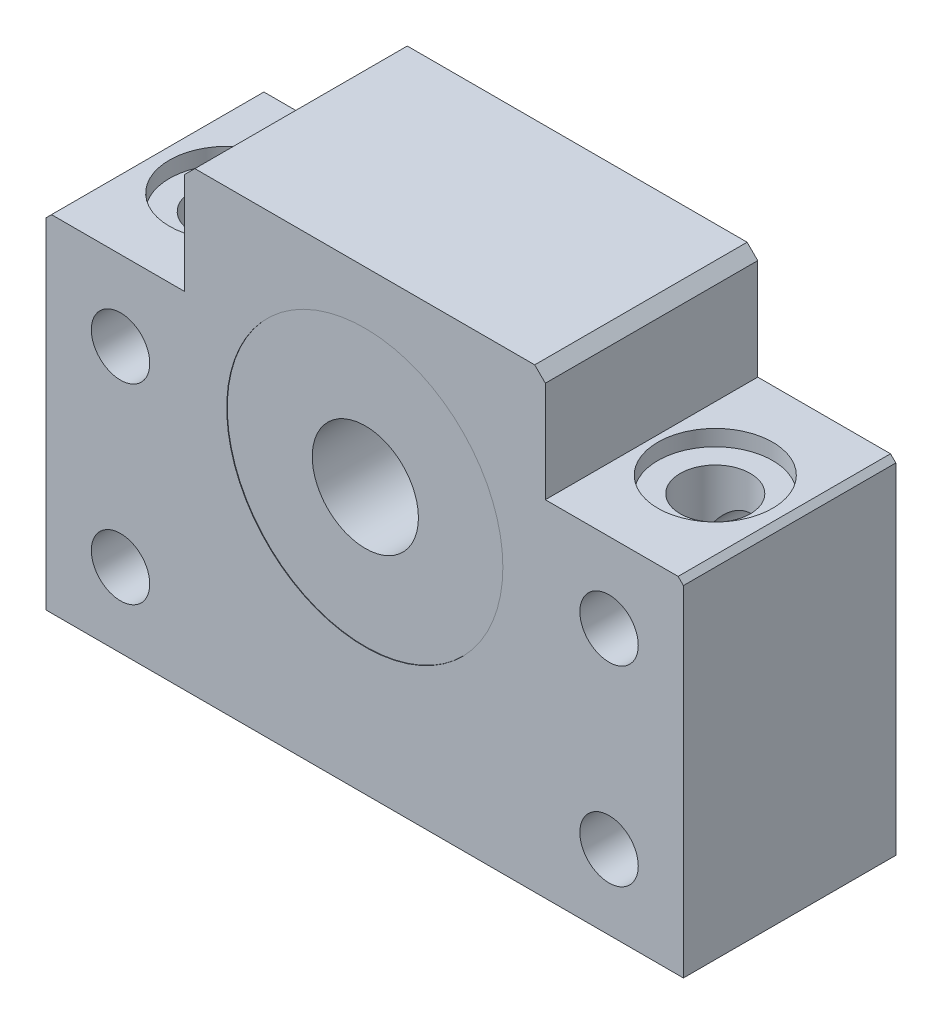
SolidWorks part; units mm, degrees
material "6061-T6 (SS)"
ref_plane "Спереди" through (0, 0, 0) normal (0, 0, 1) x (1, 0, 0)
ref_plane "Сверху" through (0, 0, 0) normal (0, 1, 0) x (1, 0, 0)
ref_plane "Справа" through (0, 0, 0) normal (1, 0, 0) x (0, 0, -1)
sketch "Эскиз1" plane through (0, 0, 0) normal (0, 0, 1) x (1, 0, 0)
  line L0 (-30, -25) -> (-30, 7)
  line L1 (0, -25) -> (0, 18) construction
  line L2 (-30, -25) -> (30, -25)
  line L3 (-29.5, 7.5) -> (-17, 7.5)
  line L4 (17, 17) -> (17, 7.5)
  line L5 (-27.8123, 0) -> (-18.3765, 0) construction
  line L6 (-23, -25) -> (-23, 7.5) construction
  line L7 (-18.3765, -18) -> (-27.8123, -18) construction
  line L8 (18.3765, -18) -> (27.8123, -18) construction
  line L9 (23, -25) -> (23, 7.5) construction
  line L10 (27.8123, 0) -> (18.3765, 0) construction
  line L11 (-16, 18) -> (-17, 17)
  line L12 (29.5, 7.5) -> (17, 7.5)
  line L13 (30, -25) -> (30, 7)
  line L14 (16, 18) -> (-16, 18)
  line L15 (-30, 7) -> (-29.5, 7.5)
  line L16 (-17, 17) -> (-17, 7.5)
  line L17 (16, 18) -> (17, 17)
  line L18 (30, 7) -> (29.5, 7.5)
  circle A0 centre (-23, 0) radius 2.75
  circle A1 centre (-23, -18) radius 2.75
  circle A2 centre (23, -18) radius 2.75
  circle A3 centre (23, 0) radius 2.75
  circle A4 centre (0, 0) radius 13
  point P1 (-30, 7.5)
  point P8 (17, 18)
  point P29 (30, 7.5)
  point P36 (-17, 18)
  dimension "D1" = 60
  dimension "D2" = 46
  dimension "D8" = 5.5
  dimension "D3" = 30
  dimension "D4" = 18
  dimension "D5" = 25
  dimension "D6" = 32.5
  dimension "D7" = 43
  dimension "D9" = 34
extrude "Бобышка-Вытянуть1" add sketch "Эскиз1" along normal blind 10 and the other way blind 10
sketch "Эскиз2" plane through (0, 0, 0) normal (0, 1, 0) x (1, 0, 0)
  line L1 (-23, 10) -> (-23, -10) construction
  line L2 (-30, 0) -> (30, 0) construction
  line L8 (23, 10) -> (23, -10) construction
  circle A0 centre (-23, 0) radius 3.3
  circle A1 centre (23, 0) radius 3.3
extrude "Вырез-Вытянуть1" cut sketch "Эскиз2" against normal through all from offset 7.5
sketch "Эскиз3" plane through (0, 0, 0) normal (0, 1, 0) x (1, 0, 0)
  circle A0 centre (-23, 0) radius 5.4
  circle A1 centre (23, 0) radius 5.4
extrude "Вырез-Вытянуть2" cut sketch "Эскиз3" against normal blind 1.5 from offset 7.5
sketch "Эскиз4" plane through (0, 0, 0) normal (0, 0, 1) x (1, 0, 0)
  circle A0 centre (0, 0) radius 13
  circle A1 centre (0, 0) radius 5
extrude "Бобышка-Вытянуть2" add sketch "Эскиз4" along normal blind 4 and the other way blind 4 from offset 5.95
